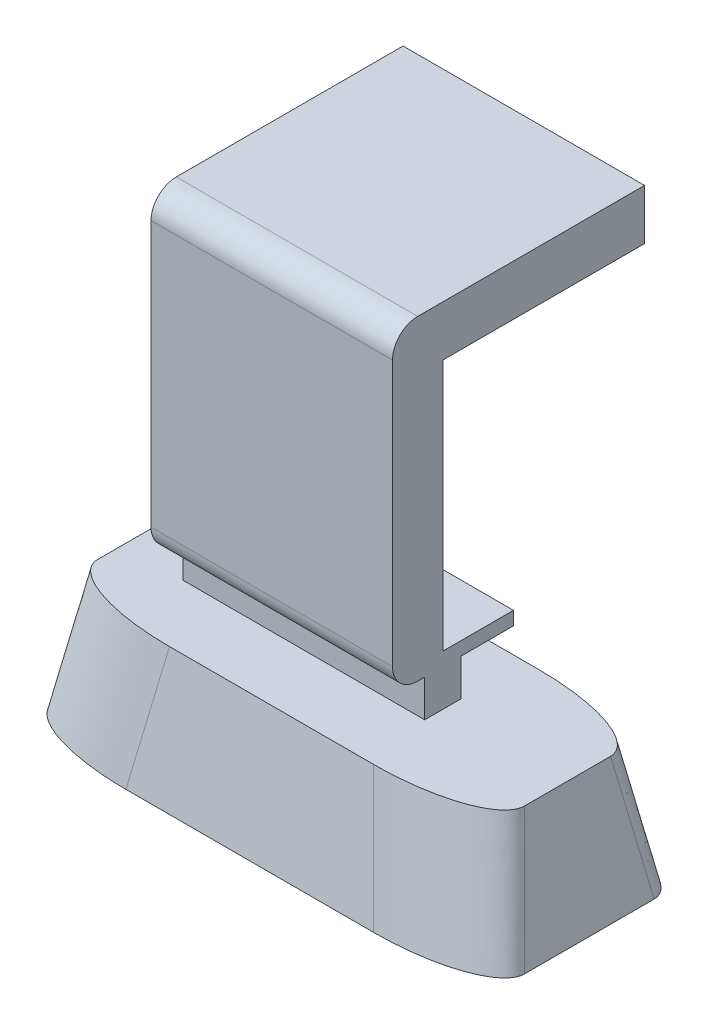
SolidWorks part; units mm, degrees
ref_plane "Front Plane" through (0, 0, 0) normal (0, 0, 1) x (1, 0, 0)
ref_plane "Top Plane" through (0, 0, 0) normal (0, 1, 0) x (1, 0, 0)
ref_plane "Right Plane" through (0, 0, 0) normal (1, 0, 0) x (0, 0, -1)
sketch "Sketch1" plane through (0, 0, 0) normal (0, 1, 0) x (1, 0, 0)
  line L1 (-19.05, 15.75) -> (52.07, 15.75)
  line L2 (-19.05, 15.75) -> (-19.05, -15.75)
  line L3 (-19.05, -15.75) -> (52.07, -15.75)
  line L4 (52.07, 15.75) -> (52.07, -15.75)
  point P4 (-19.05, 0)
  dimension "D1" = 71.12
  dimension "D2" = 31.5
  dimension "D3" = 19.05
extrude "Boss-Extrude1" add sketch "Sketch1" along normal blind 18.6944 draft 10
fillet "Fillet1" radius 16.764 4 edges at (50.4218, 9.3472, 14.1018) (-17.4018, 9.3472, -14.1018) (50.4218, 9.3472, -14.1018) (-17.4018, 9.3472, 14.1018)
sketch "Sketch3" plane through (0, 0, 0) normal (0, -1, 0) x (1, 0, 0)
  circle A0 centre (0, 0) radius 4
  dimension "D1" = 8
extrude "Cut-Extrude1" cut sketch "Sketch3" against normal blind 2.54
chamfer "Chamfer1" distance 2.54 angle 45 1 edges at (0, 0, -4)
ref_plane "Plane1" through (-19.05, 0, 0) normal (1, 0, 0) x (0, 0, -1)
sketch "Sketch4" plane through (0, 0, 0) normal (1, 0, 0) x (0, 0, -1)
  line L20 (0, 0) -> (0, 99.0964) construction
  line L21 (-7.62, 64.4144) -> (0, 64.4144) construction
  line L22 (2.7563, 24.2824) -> (-2.7563, 24.2824) construction
  line L23 (2.7563, 24.2824) -> (-2.7563, 18.6944) construction
  line L24 (2.7563, 18.6944) -> (-2.7563, 24.2824) construction
  line L25 (2.7563, 24.2824) -> (-2.7563, 24.2824) construction
  line L26 (-7.62, 64.4144) -> (0, 64.4144) construction
  line L27 (30.48, 64.4144) -> (30.48, 72.0344)
  line L28 (-3.81, 72.0344) -> (30.48, 72.0344)
  line L29 (-7.62, 64.4144) -> (-7.62, 68.2244)
  line L30 (0, 64.4144) -> (30.48, 64.4144)
  line L31 (-2.7563, 24.2824) -> (-3.81, 24.2824)
  line L32 (-2.7563, 18.6944) -> (-2.7563, 24.2824)
  line L33 (2.7563, 18.6944) -> (-2.7563, 18.6944)
  line L34 (2.7563, 18.6944) -> (2.7563, 24.2824)
  line L35 (10.668, 26.3144) -> (10.668, 24.2824)
  line L36 (0, 26.3144) -> (10.668, 26.3144)
  line L37 (0, 64.4144) -> (0, 26.3144)
  line L38 (-7.62, 28.0924) -> (-7.62, 64.4144)
  line L39 (10.668, 24.2824) -> (2.7563, 24.2824)
  arc A2 (-7.62, 68.2244) -> (-3.81, 72.0344) centre (-3.81, 68.2244) cw
  arc A3 (-3.81, 24.2824) -> (-7.62, 28.0924) centre (-3.81, 28.0924) cw
  point P7 (0, 21.4884)
  point P68 (-7.62, 72.0344)
extrude "Boss-Extrude2" add sketch "Sketch4" against normal offset from surface (6.55 mm away) 12.5 from offset 0 up to plane "Plane1"
sketch "Sketch5" plane through (0, 0, 0) normal (1, 0, 0) x (0, 0, -1)
  line L12 (-7.62, 68.2244) -> (-7.62, 28.0924)
  line L13 (-3.81, 24.2824) -> (-2.7563, 24.2824)
  line L14 (-2.7563, 24.2824) -> (-2.7563, 18.6944)
  line L15 (-2.7563, 18.6944) -> (2.7563, 18.6944)
  line L16 (2.7563, 18.6944) -> (2.7563, 24.2824)
  line L17 (2.7563, 24.2824) -> (10.668, 24.2824)
  line L18 (10.668, 24.2824) -> (10.668, 26.3144)
  line L19 (10.668, 26.3144) -> (0, 26.3144)
  line L20 (0, 26.3144) -> (0, 64.4144)
  line L21 (0, 64.4144) -> (30.48, 64.4144)
  line L22 (30.48, 64.4144) -> (30.48, 72.0344)
  line L23 (30.48, 72.0344) -> (-3.81, 72.0344)
  line L24 (-7.62, 68.2244) -> (-7.62, 28.0924)
  line L25 (-3.81, 24.2824) -> (-2.7563, 24.2824)
  line L26 (-2.7563, 24.2824) -> (-2.7563, 18.6944)
  line L27 (-2.7563, 18.6944) -> (2.7563, 18.6944)
  line L28 (2.7563, 18.6944) -> (2.7563, 24.2824)
  line L29 (2.7563, 24.2824) -> (10.668, 24.2824)
  line L30 (10.668, 24.2824) -> (10.668, 26.3144)
  line L31 (10.668, 26.3144) -> (0, 26.3144)
  line L32 (0, 26.3144) -> (0, 64.4144)
  line L33 (0, 64.4144) -> (30.48, 64.4144)
  line L34 (30.48, 64.4144) -> (30.48, 72.0344)
  line L35 (30.48, 72.0344) -> (-3.81, 72.0344)
  arc A2 (-7.62, 28.0924) -> (-3.81, 24.2824) centre (-3.81, 28.0924) ccw
  arc A3 (-3.81, 72.0344) -> (-7.62, 68.2244) centre (-3.81, 68.2244) ccw
  arc A4 (-7.62, 28.0924) -> (-3.81, 24.2824) centre (-3.81, 28.0924) ccw
  arc A5 (-3.81, 72.0344) -> (-7.62, 68.2244) centre (-3.81, 68.2244) ccw
  dimension "D1" = 0
extrude "Boss-Extrude3" add sketch "Sketch5" along normal offset from surface (29.95 mm away) 36.5 up to face at (-6.55, 39.7401, -4.1327)
